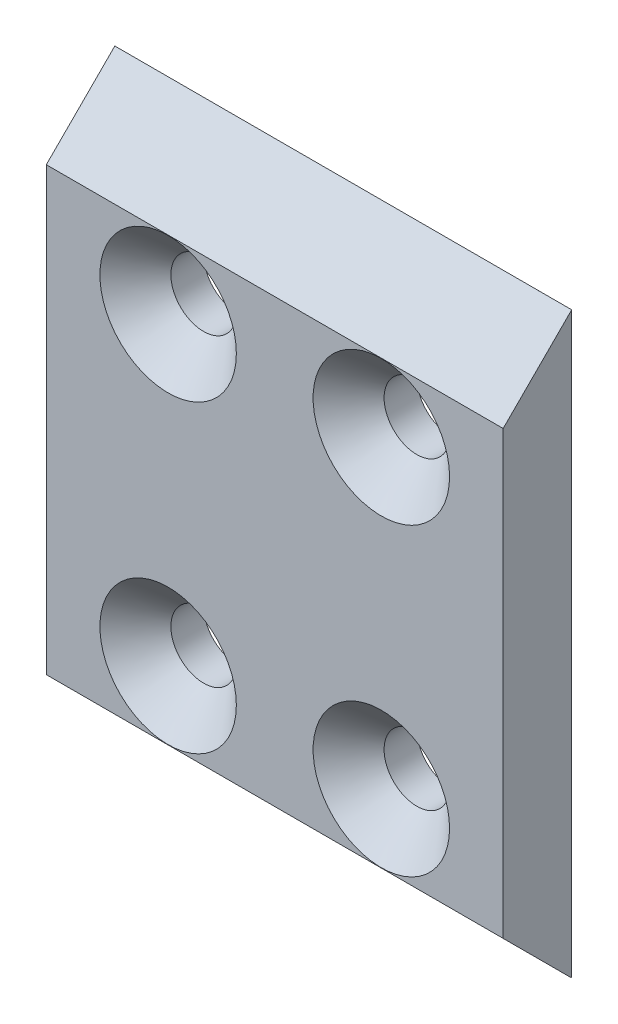
SolidWorks part; units mm, degrees
material "锌 AC41A 合金，作为铸件"
ref_plane "前视基准面" through (0, 0, 0) normal (0, 0, 1) x (1, 0, 0)
ref_plane "上视基准面" through (0, 0, 0) normal (0, 1, 0) x (1, 0, 0)
ref_plane "右视基准面" through (0, 0, 0) normal (1, 0, 0) x (0, 0, -1)
other "Configuration Table"
sketch "草图1" plane through (0, 0, 0) normal (0, 0, 1) x (1, 0, 0)
  line L0 (0, 19) -> (30, 19) construction
  line L1 (0, 0) -> (30, 0)
  line L2 (0, 0) -> (0, 38)
  line L3 (0, 38) -> (30, 38)
  line L4 (30, 0) -> (30, 38)
  dimension "D1" = 30
  dimension "D2" = 38
extrude "凸台-拉伸1" add sketch "草图1" along normal blind 4.5
chamfer "倒角1" distance 4.5 angle 45 2 edges at (15, 0, 4.5) (15, 38, 4.5)
sketch "草图2" plane through (0, 0, 4.5) normal (0, 0, 1) x (1, 0, 0)
  line L0 (15, 33.5) -> (15, 4.5) construction
  line L1 (30, 33.5) -> (0, 33.5) construction
  line L2 (0, 4.5) -> (30, 4.5) construction
  line L3 (0, 19) -> (30, 19) construction
  line L4 (30, 4.5) -> (30, 33.5) construction
  line L5 (0, 33.5) -> (0, 4.5) construction
  point P13 (8, 29)
  point P14 (22, 29)
  point P16 (22, 9)
  point P17 (8, 9)
  dimension "D1" = 7
  dimension "D2" = 10
  dimension "D3" = 2
  dimension "D4" = 2
hole_wizard "M4 六角凹锥坑螺钉的锥形沉头孔1" positions "草图2" profile "草图3" countersink size "M4" standard "ISO" end condition through all
sketch "草图3" plane through (8, 9, 4.5) normal (1, 0, 0) x (0, -1, 0)
  line L0 (0, 0) -> (0, 4.5)
  line L1 (0, 4.5) -> (2.15, 4.5)
  line L2 (2.15, 4.5) -> (2.15, 2.33)
  line L3 (2.15, 2.33) -> (4.48, 0)
  line L5 (4.48, 0) -> (0, 0)
  line L6 (-2.15, 2.33) -> (-4.48, 0) construction
  line L11 (0, -6.35) -> (0, 107.95) construction
  dimension "通孔孔直径" = 4.3
  dimension "通孔孔深度" = 4.5
  dimension "近端锥形沉头孔直径" = 8.96
  dimension "近端锥形沉头孔角度" = 90
